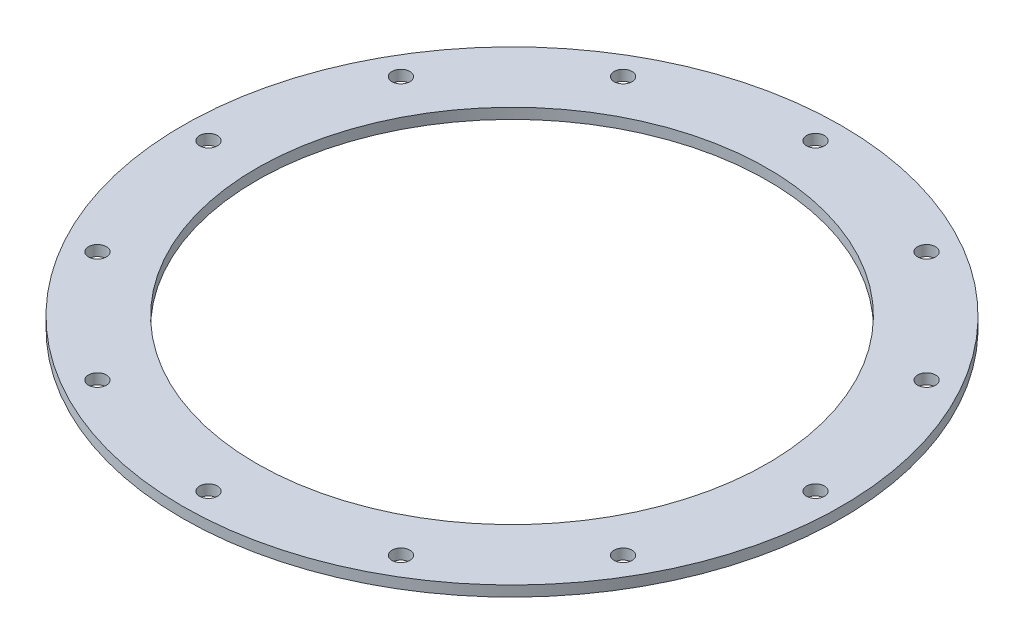
SolidWorks part; units mm, degrees
material "PTFE (general)"
ref_plane "Front Plane" through (0, 0, 0) normal (0, 0, 1) x (1, 0, 0)
ref_plane "Top Plane" through (0, 0, 0) normal (0, 1, 0) x (1, 0, 0)
ref_plane "Right Plane" through (0, 0, 0) normal (1, 0, 0) x (0, 0, -1)
ref_axis "Axis1" through (0, 55, 0) along (0, -1, 0)
sketch "Sketch1" plane through (0, 0, 0) normal (0, 0, 1) x (1, 0, 0)
  line L0 (-38.608, 0) -> (0, 0) construction
  line L1 (-38.608, 0) -> (-49.784, 0)
  line L2 (-38.608, 0) -> (-38.608, 1.5875)
  line L3 (-38.608, 1.5875) -> (-49.784, 1.5875)
  line L4 (-49.784, 0) -> (-49.784, 1.5875)
  line L7 (0, 1.5875) -> (-38.1, 1.5875) construction
  point P12 (-49.784, 0)
  point P18 (-38.608, 1.5875)
  dimension "D1" = 11.176
revolve "Main" add sketch "Sketch1" angle 360 about axis through (0, 55, 0) along (0, -1, 0)
sketch "Hole Location" plane through (0, 0, 0) normal (0, 1, 0) x (1, 0, 0)
  line L0 (0, 0) -> (-45.847, 0) construction
  circle A0 centre (0, 0) radius 45.847 construction
  dimension "D1" = 91.694
hole_wizard "#36 (0.1065) Diameter Hole1" positions "Sketch3" profile "Sketch5" hole size "#36" standard "ANSI Inch" end condition through all
sketch "Sketch3" plane through (0, 0, 0) normal (0, -1, 0) x (-1, 0, 0)
  point P0 (45.847, 0)
sketch "Sketch5" plane through (-45.847, 0, 0) normal (1, 0, 0) x (0, 0, -1)
  line L0 (0, 0) -> (0, 1.5875)
  line L1 (0, 1.5875) -> (1.3525, 1.5875)
  line L2 (1.3525, 1.5875) -> (1.3525, 0)
  line L5 (1.3525, 0) -> (0, 0)
  line L11 (0, -6.35) -> (0, 107.95) construction
  dimension "Thru Hole Dia." = 2.7051
  dimension "Thru Hole Depth" = 1.5875
pattern_circular "Screw Passthroughs" count 12 over 360 about axis through (0, 55, 0) along (0, -1, 0) of "#36 (0.1065) Diameter Hole1"
equation "\"D1@Hole Location\"=\"TANK DIAMETER@Cryo Tank.Assembly\"+\"GASKET SEAT THICKNESS@Cryo Tank.Assembly\"+\"LINER THICKNESS@Cryo Tank.Assembly\"+\"LINER COMPRESSION DELTA@Cryo Tank.Assembly\"+\"SHRINK FIT DELTA@Cryo Tank.Assembly\""
equation "\"D1@Sketch1\"=\"GASKET SEAT THICKNESS@Cryo Tank.Assembly\"-\"LINER COMPRESSION DELTA@Cryo Tank.Assembly\""
